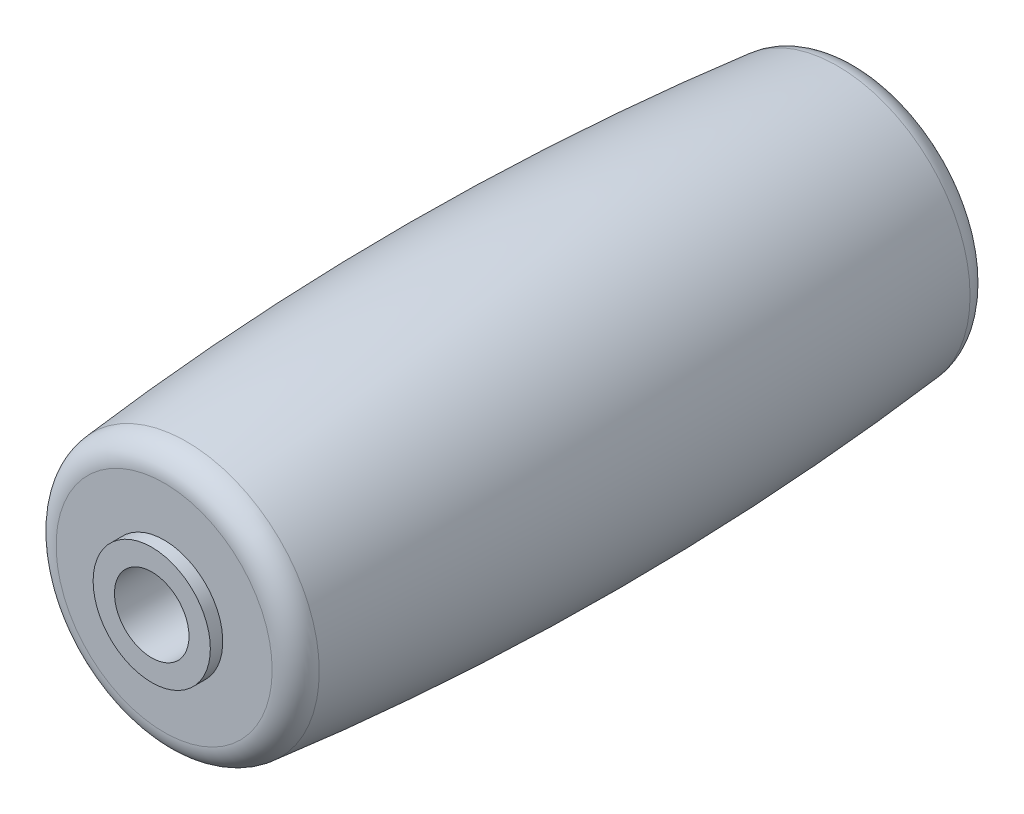
SolidWorks part; units mm, degrees
ref_plane "前视基准面" through (0, 0, 0) normal (0, 0, 1) x (1, 0, 0)
ref_plane "上视基准面" through (0, 0, 0) normal (0, 1, 0) x (1, 0, 0)
ref_plane "右视基准面" through (0, 0, 0) normal (1, 0, 0) x (0, 0, -1)
sketch "草图1" plane through (0, 0, 0) normal (1, 0, 0) x (0, 0, -1)
  line L0 (-14, 4.3486) -> (-14, 0)
  line L1 (-14, 0) -> (14, 0)
  line L2 (14, 0) -> (14, 4.3486)
  line L3 (0, 0) -> (0, 6) construction
  arc A0 (-13.1, 5.3436) -> (13.1, 5.3436) centre (0, -125.0417) cw
  arc A1 (14, 4.3486) -> (13.1, 5.3436) centre (13, 4.3486) ccw
  arc A2 (-14, 4.3486) -> (-13.1, 5.3436) centre (-13, 4.3486) cw
  point P10 (14, 5.25)
  point P13 (-14, 5.25)
  dimension "D4" = 1
  dimension "D1" = 28
  dimension "D2" = 5.25
  dimension "D3" = 6
revolve "旋转1" add sketch "草图1" angle 360 about L1
sketch "草图2" plane through (0, 0, 14) normal (0, 0, 1) x (1, 0, 0)
  circle A0 centre (0, 0) radius 3.75
  circle A1 centre (0, 0) radius 1.5
  dimension "D1" = 7.5
  dimension "D2" = 3
extrude "切除-拉伸1" cut sketch "草图2" against normal up to surface (28 mm away) contours A1 up to face at (4.3486, 0, -14)
extrude "切除-拉伸2" cut sketch "草图2<4>" against normal blind 1.5
sketch "草图2<4>" plane through (0, 0, 14) normal (0, 0, 1) x (1, 0, 0) same geometry as "草图2"
mirror "镜向1" about plane through (0, 0, 0) normal (0, 0, 1) of "切除-拉伸2"
sketch "草图4" plane through (0, 0, 12.5) normal (0, 0, 1) x (1, 0, 0)
  circle A1 centre (0, 0) radius 3.75
  circle A2 centre (0, 0) radius 3.75
  circle M2 centre (0, 0) radius 1.5
  circle M3 centre (0, 0) radius 3.75
  dimension "D1" = 0
extrude "凸台-拉伸2" add sketch "草图4" along normal blind 1.5 contours M3 M2 region at (-3.6439, 0, 12.5)
sketch "草图5" plane through (0, 0, 14) normal (0, 0, 1) x (1, 0, 0)
  circle A0 centre (0, 0) radius 2.3595
  circle M3 centre (0, 0) radius 1.5
extrude "凸台-拉伸3" add sketch "草图5" along normal blind 0.5 contours A0 M3 region at (-2.2928, 0, 14)
mirror "镜向4" about plane through (0, 0, 0) normal (0, 0, 1) of "凸台-拉伸3", "凸台-拉伸2"
